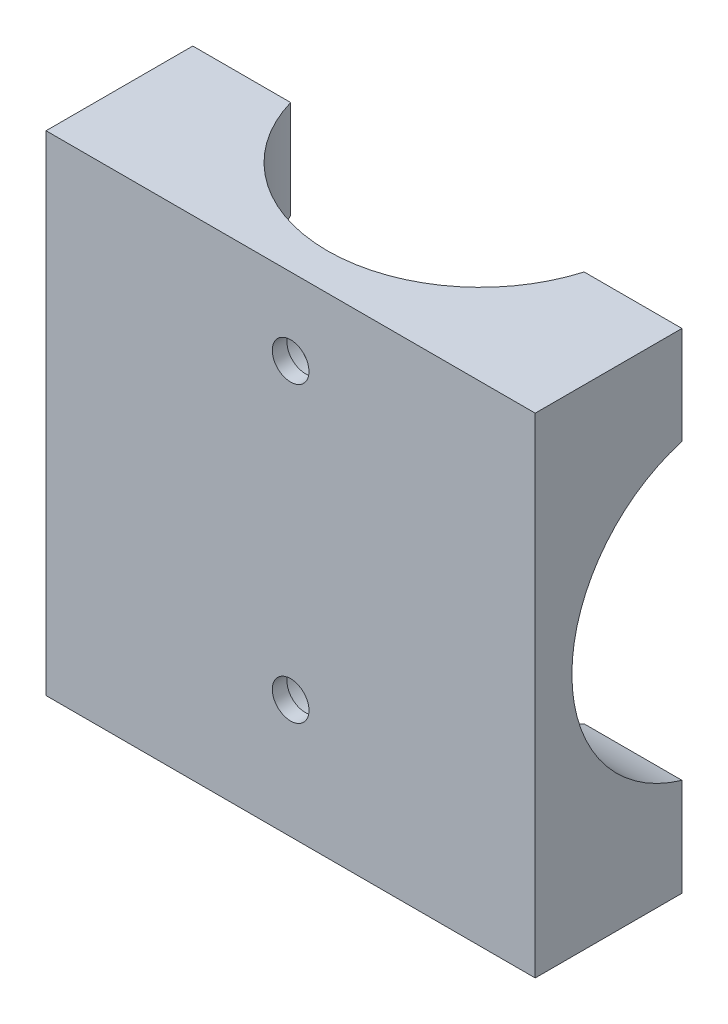
SolidWorks part; units mm, degrees
ref_plane "Front Plane" through (0, 0, 0) normal (0, 0, 1) x (1, 0, 0)
ref_plane "Top Plane" through (0, 0, 0) normal (0, 1, 0) x (1, 0, 0)
ref_plane "Right Plane" through (0, 0, 0) normal (1, 0, 0) x (0, 0, -1)
sketch "Sketch1" plane through (0, 0, 0) normal (0, 0, 1) x (1, 0, 0)
  line L1 (-30.0552, 14.8619) -> (9.9448, 14.8619)
  line L2 (-30.0552, 14.8619) -> (-30.0552, -25.1381)
  line L3 (-30.0552, -25.1381) -> (9.9448, -25.1381)
  line L4 (9.9448, 14.8619) -> (9.9448, -25.1381)
  dimension "D1" = 40
  dimension "D2" = 40
extrude "Boss-Extrude1" add sketch "Sketch1" along normal blind 12
ref_plane "Plane1" through (0, 14.8619, 0) normal (0, 1, 0) x (1, 0, 0)
sketch "Sketch3" plane through (0, 14.8619, 0) normal (0, 1, 0) x (1, 0, 0)
  circle A0 centre (-10.0552, 3.5) radius 12.5
extrude "Cut-Extrude3" cut sketch "Sketch3" against normal blind 40
ref_plane "Plane3" through (9.9448, 0, 0) normal (1, 0, 0) x (0, 0, -1)
sketch "Sketch11" plane through (9.9448, 0, 0) normal (1, 0, 0) x (0, 0, -1)
  circle A0 centre (3.5, -5.1381) radius 12.5
extrude "Cut-Extrude4" cut sketch "Sketch11" against normal blind 40
ref_plane "Plane4" through (0, 0, 12) normal (0, 0, 1) x (1, 0, 0)
sketch "Sketch14" plane through (0, 0, 12) normal (0, 0, 1) x (1, 0, 0)
  circle A0 centre (-10.0552, 8.5619) radius 1.5
  circle A1 centre (-10.0552, -15.4381) radius 1.5
  circle A2 centre (-10.0552, 8.5619) radius 3
  circle A3 centre (-10.0552, -15.4381) radius 3
  dimension "D1" = 24
extrude "Cut-Extrude7" cut sketch "Sketch14" against normal blind 30 contours A3 | A2
extrude "Boss-Extrude2" add sketch "Sketch14<5>" against normal blind 1.2
sketch "Sketch14<5>" plane through (0, 0, 12) normal (0, 0, 1) x (1, 0, 0) same geometry as "Sketch14"
